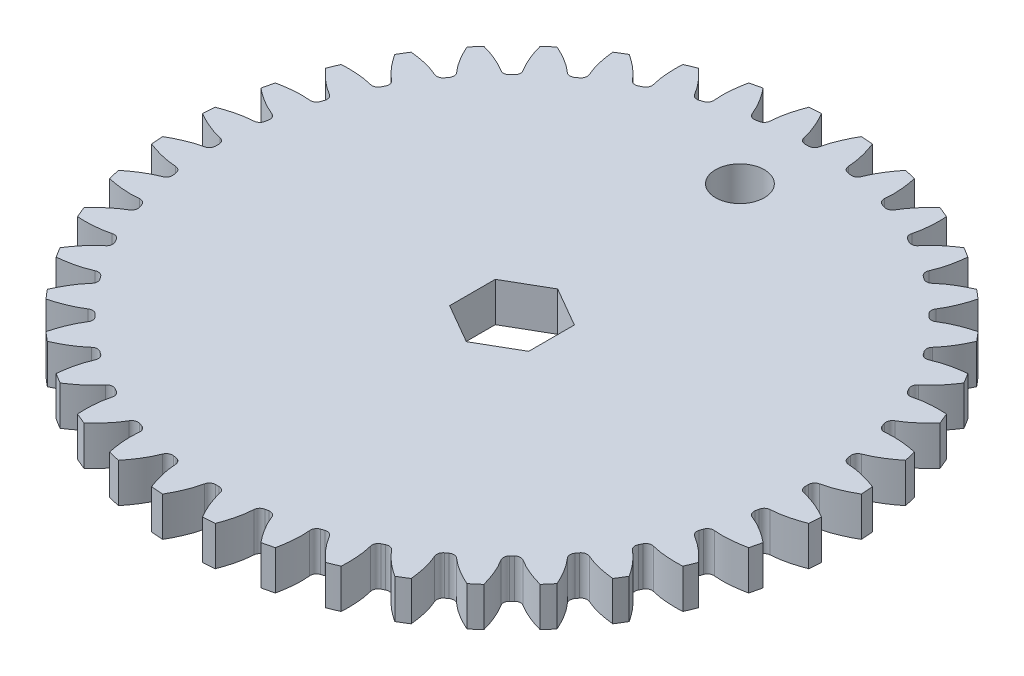
SolidWorks part; units mm, degrees
ref_plane "Front Plane" through (0, 0, 0) normal (0, 0, 1) x (1, 0, 0)
ref_plane "Top Plane" through (0, 0, 0) normal (0, 1, 0) x (1, 0, 0)
ref_plane "Right Plane" through (0, 0, 0) normal (1, 0, 0) x (0, 0, -1)
sketch "Sketch2" plane through (0, 0, 0) normal (0, 1, 0) x (1, 0, 0)
  circle A0 centre (0, 0) radius 53.34
  dimension "D1" = 106.68
extrude "Boss-Extrude1" add sketch "Sketch2" along normal blind 12.7
sketch "Sketch3" plane through (0, 0, 0) normal (0, -1, 0) x (-1, 0, 0)
  line L0 (0, 0) -> (47.7222, -1.163) construction
  line L1 (0, 0) -> (47.7222, 1.163) construction
  line L2 (47.7222, -1.163) -> (47.6109, -1.1603)
  line L3 (47.7222, 1.163) -> (47.6109, 1.1603)
  circle A0 centre (0, 0) radius 53.34
  circle A1 centre (0, 0) radius 50.8
  circle A2 centre (0, 0) radius 47.752
  circle A3 centre (0, 0) radius 47.625
  spline S0 degree 4 poles (47.7222, 1.163) (47.731, 1.1633) (47.7556, 1.1645) (47.802, 1.1678) (47.8777, 1.1747) (47.9741, 1.186) (48.0986, 1.2033) (48.2451, 1.2271) (48.4058, 1.257) (48.5805, 1.2934) (48.7546, 1.3332) (48.928, 1.3762) (49.1005, 1.4219) (49.3093, 1.4808) (49.5592, 1.5562) (49.8507, 1.6513) (50.1805, 1.7675) (50.5158, 1.8948) (50.845, 2.0273) (51.1768, 2.1695) (51.4972, 2.313) (51.8289, 2.4707) (52.1347, 2.6205) (52.4761, 2.7979) (52.7513, 2.9438) (53.113, 3.1463) (53.3263, 3.2689) (53.5754, 3.4159) (53.6857, 3.483) (53.7537, 3.5243) knots 0 0 0 0 0 0.005377 0.015084 0.028532 0.04661 0.064855 0.092111 0.119476 0.146842 0.174209 0.201575 0.228941 0.256307 0.307035 0.361767 0.4165 0.471232 0.525964 0.580697 0.635429 0.690161 0.744894 0.799626 0.854358 0.909091 0.954545 1 1 1 1 1 construction
  spline S1 degree 4 poles (47.7222, 1.163) (47.731, 1.1633) (47.7556, 1.1645) (47.802, 1.1678) (47.8777, 1.1747) (47.9741, 1.186) (48.0986, 1.2033) (48.2451, 1.2271) (48.4058, 1.257) (48.5805, 1.2934) (48.7546, 1.3332) (48.928, 1.3762) (49.1005, 1.4219) (49.3093, 1.4808) (49.5592, 1.5562) (49.8507, 1.6513) (50.1805, 1.7675) (50.5158, 1.8948) (50.845, 2.0273) (51.1768, 2.1695) (51.4972, 2.313) (51.8289, 2.4707) (52.1347, 2.6205) (52.4761, 2.7979) (52.7513, 2.9438) (53.0346, 3.1024) (53.1723, 3.1808) (53.2426, 3.2213) knots 0 0 0 0 0 0.005377 0.015084 0.028532 0.04661 0.064855 0.092111 0.119476 0.146842 0.174209 0.201575 0.228941 0.256307 0.307035 0.361767 0.4165 0.471232 0.525964 0.580697 0.635429 0.690161 0.744894 0.799626 0.854358 0.909091 0.909091 0.909091 0.909091 0.909091
  spline S2 degree 4 poles (47.7222, -1.163) (47.731, -1.1633) (47.7556, -1.1645) (47.802, -1.1678) (47.8777, -1.1747) (47.9741, -1.186) (48.0986, -1.2033) (48.2451, -1.2271) (48.4058, -1.257) (48.5805, -1.2934) (48.7546, -1.3332) (48.928, -1.3762) (49.1005, -1.4219) (49.3093, -1.4808) (49.5592, -1.5562) (49.8507, -1.6513) (50.1805, -1.7675) (50.5158, -1.8948) (50.845, -2.0273) (51.1768, -2.1695) (51.4972, -2.313) (51.8289, -2.4707) (52.1347, -2.6205) (52.4761, -2.7979) (52.7513, -2.9438) (53.113, -3.1463) (53.3263, -3.2689) (53.5754, -3.4159) (53.6857, -3.483) (53.7537, -3.5243) knots 0 0 0 0 0 0.005377 0.015084 0.028532 0.04661 0.064855 0.092111 0.119476 0.146842 0.174209 0.201575 0.228941 0.256307 0.307035 0.361767 0.4165 0.471232 0.525964 0.580697 0.635429 0.690161 0.744894 0.799626 0.854358 0.909091 0.954545 1 1 1 1 1 construction
  spline S3 degree 4 poles (47.7222, -1.163) (47.731, -1.1633) (47.7556, -1.1645) (47.802, -1.1678) (47.8777, -1.1747) (47.9741, -1.186) (48.0986, -1.2033) (48.2451, -1.2271) (48.4058, -1.257) (48.5805, -1.2934) (48.7546, -1.3332) (48.928, -1.3762) (49.1005, -1.4219) (49.3093, -1.4808) (49.5592, -1.5562) (49.8507, -1.6513) (50.1805, -1.7675) (50.5158, -1.8948) (50.845, -2.0273) (51.1768, -2.1695) (51.4972, -2.313) (51.8289, -2.4707) (52.1347, -2.6205) (52.4761, -2.7979) (52.7513, -2.9438) (53.0346, -3.1024) (53.1723, -3.1808) (53.2426, -3.2213) knots 0 0 0 0 0 0.005377 0.015084 0.028532 0.04661 0.064855 0.092111 0.119476 0.146842 0.174209 0.201575 0.228941 0.256307 0.307035 0.361767 0.4165 0.471232 0.525964 0.580697 0.635429 0.690161 0.744894 0.799626 0.854358 0.909091 0.909091 0.909091 0.909091 0.909091
  dimension "D1" = 106.68
  dimension "D2" = 101.6
  dimension "D3" = 95.504
  dimension "D4" = 95.25
extrude "Cut-Extrude1" cut sketch "Sketch3" against normal blind 12.7 contours A1 S3 A0 S1 | A2 S3 A1 S1 | L2 S3 A2 S1 L3 A3 region at (-47.6838, 0, 0) region at (-49.4115, 0, 0) region at (-52.1487, 0, 0)
fillet "Fillet2" radius 1.016 2 edges at (-47.6109, 6.35, -1.1603) (-47.6109, 6.35, 1.1603)
pattern_circular "CirPattern1" count 40 over 360 about axis through (0, 12.7, 0) along (0, 1, 0) of "Fillet2", "Cut-Extrude1"
sketch "Sketch4" plane through (0, 12.7, 0) normal (0, 1, 0) x (1, 0, 0)
  circle A0 centre (0, 0) radius 4.0957
  dimension "D1" = 8.1915
extrude "Cut-Extrude2" cut sketch "Sketch4" against normal through all
sketch "Sketch5" plane through (0, 12.7, 0) normal (0, 1, 0) x (1, 0, 0)
  line L1 (0, 7.3763) -> (-6.3881, 3.6882)
  line L2 (-6.3881, 3.6882) -> (-6.3881, -3.6882)
  line L3 (-6.3881, -3.6882) -> (0, -7.3763)
  line L4 (0, -7.3763) -> (6.3881, -3.6882)
  line L5 (6.3881, -3.6882) -> (6.3881, 3.6882)
  line L6 (6.3881, 3.6882) -> (0, 7.3763)
  circle A0 centre (0, 0) radius 6.3881 construction
  dimension "D1" = 12.7762
extrude "Cut-Extrude3" cut sketch "Sketch5" against normal blind 6.35
sketch "Sketch6" plane through (0, 12.7, 0) normal (0, 1, 0) x (1, 0, 0)
  line L0 (0, 0) -> (0, 36.83) construction
  circle A0 centre (0, 36.83) radius 3.937
  dimension "D2" = 7.874
  dimension "D1" = 36.83
extrude "Cut-Extrude4" cut sketch "Sketch6" against normal through all both and the other way through all
sketch "Sketch7" plane through (0, 6.35, 0) normal (0, 1, 0) x (1, 0, 0)
  circle A0 centre (0, 0) radius 100.3623
extrude "Cut-Extrude5" cut sketch "Sketch7" against normal through all
equation "\"DiametralPitch\"= 10"
equation "\"NumTeeth\"= 40"
equation "\"PressureAngle\"= 20deg"
equation "\"Addendum\"= 1 / \"DiametralPitch\""
equation "\"Dedendum\"= 1.25 / \"DiametralPitch\""
equation "\"WorkingDepth\"= 2 / \"DiametralPitch\""
equation "\"WholeDepth\"= 2.25 / \"DiametralPitch\""
equation "\"Clearance\"= 0.3 / \"DiametralPitch\""
equation "\"ToothThickness\"= 1.5708 / \"DiametralPitch\""
equation "\"CircularPitch\"= pi / \"DiametralPitch\""
equation "\"PitchCircle\"= \"NumTeeth\" / \"DiametralPitch\""
equation "\"OutsideDiameter\"= ( \"NumTeeth\" + 2 ) / \"DiametralPitch\""
equation "\"Fillet\"= \"Clearance\" * cos ( \"PressureAngle\" ) * tan ( ( 90 + \"PressureAngle\" ) / 2 )"
equation "\"AddendumCircle\"= \"PitchCircle\" + ( 2 * \"Addendum\" )"
equation "\"DedendumCircle\"= \"PitchCircle\" - ( 2 * \"Dedendum\" )"
equation "\"BaseCircle\"= \"PitchCircle\" * cos ( \"PressureAngle\" )"
equation "\"PitchAngle\"= 360deg / \"NumTeeth\""
equation "\"Alpha\"= sqr ( \"PitchCircle\" ^ 2 - \"BaseCircle\" ^ 2 ) / \"BaseCircle\" * 180 / PI - \"PressureAngle\""
equation "\"Beta\"= ( \"PitchAngle\" / 4 - \"Alpha\" )"
equation "\"Phi\"= sqr ( ( \"AddendumCircle\" / 2 ) ^ 2 - ( \"BaseCircle\" / 2 ) ^ 2 ) / ( \"BaseCircle\" / 2 )"
